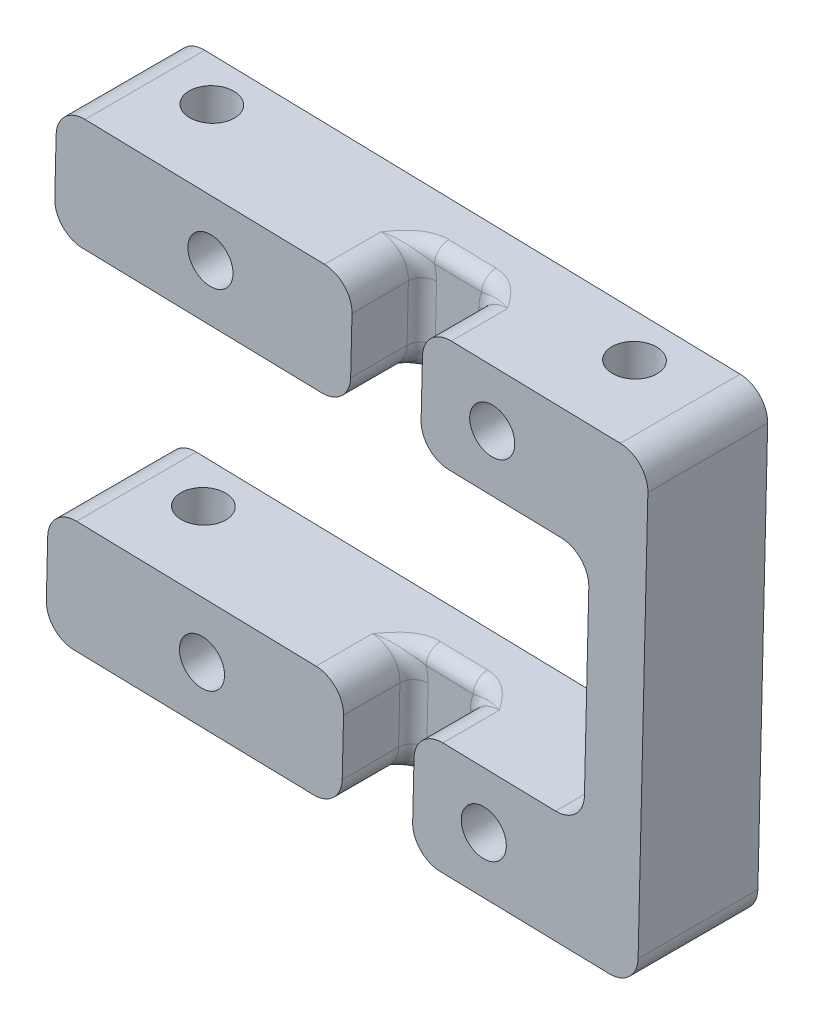
SolidWorks part; units mm, degrees
material "3003 合金"
ref_plane "前视基准面" through (0, 0, 0) normal (0, 0, 1) x (1, 0, 0)
ref_plane "上视基准面" through (0, 0, 0) normal (0, 1, 0) x (1, 0, 0)
ref_plane "右视基准面" through (0, 0, 0) normal (1, 0, 0) x (0, 0, -1)
other "Configuration Table"
sketch "草图1" plane through (0, 0, 0) normal (0, 0, 1) x (1, 0, 0)
  line L0 (19.3897, 16.0402) -> (-18.5994, 16.9503)
  line L1 (-20.6467, 14.9988) -> (-20.7425, 10.9999)
  line L2 (-18.791, 8.9526) -> (15.1993, 8.1383)
  line L3 (17.1508, 6.091) -> (16.8394, -6.9053)
  line L4 (14.7921, -8.8568) -> (-19.1981, -8.0425)
  line L5 (-21.2455, -9.994) -> (-21.3413, -13.9929)
  line L6 (-19.3897, -16.0402) -> (18.5994, -16.9503)
  line L7 (20.6467, -14.9988) -> (21.3413, 13.9929)
  arc A0 (-11.896, -12.2186) -> (-8.697, -12.2952) centre (-10.2965, -12.2569) ccw
  arc A1 (-8.697, -12.2952) -> (-11.896, -12.2186) centre (-10.2965, -12.2569) ccw
  arc A2 (-18.5994, 16.9503) -> (-20.6467, 14.9988) centre (-18.6473, 14.9509) ccw
  arc A3 (-20.7425, 10.9999) -> (-18.791, 8.9526) centre (-18.7431, 10.952) ccw
  arc A4 (17.1508, 6.091) -> (15.1993, 8.1383) centre (15.1514, 6.1389) ccw
  arc A5 (14.7921, -8.8568) -> (16.8394, -6.9053) centre (14.84, -6.8574) ccw
  arc A6 (-19.1981, -8.0425) -> (-21.2455, -9.994) centre (-19.246, -10.0419) ccw
  arc A7 (-21.3413, -13.9929) -> (-19.3897, -16.0402) centre (-19.3418, -14.0408) ccw
  arc A8 (18.5994, -16.9503) -> (20.6467, -14.9988) centre (18.6473, -14.9509) ccw
  arc A9 (21.3413, 13.9929) -> (19.3897, 16.0402) centre (19.3418, 14.0408) ccw
  arc A10 (8.697, 12.2952) -> (11.896, 12.2186) centre (10.2965, 12.2569) ccw
  arc A11 (11.896, 12.2186) -> (8.697, 12.2952) centre (10.2965, 12.2569) ccw
  arc A12 (8.0982, -12.6976) -> (11.2973, -12.7742) centre (9.6978, -12.7359) ccw
  arc A13 (11.2973, -12.7742) -> (8.0982, -12.6976) centre (9.6978, -12.7359) ccw
  arc A14 (-11.2973, 12.7742) -> (-8.0982, 12.6976) centre (-9.6978, 12.7359) ccw
  arc A15 (-8.0982, 12.6976) -> (-11.2973, 12.7742) centre (-9.6978, 12.7359) ccw
extrude "凸台-拉伸1" add sketch "草图1" along normal blind 8.5
sketch "草图2" plane through (-0.3952, -16.4953, 0) normal (-0.024, -0.9997, 0) x (0.9997, -0.024, 0)
  line L0 (-19, 8.5) -> (19, 8.5) construction
  line L1 (5, 8.5) -> (0, 8.5)
  line L2 (5, 8.5) -> (5, 3.5)
  line L3 (5, 3.5) -> (0, 3.5)
  line L4 (0, 8.5) -> (0, 3.5)
  line L5 (21, 8.5) -> (21, 0) construction
  line L6 (-19, 0) -> (19, 0) construction
  line L7 (-21, 8.5) -> (-21, 0) construction
  circle A0 centre (14.5, 3) radius 1.6
  circle A1 centre (-15.5, 3) radius 1.6
  dimension "D4" = 3.2
  dimension "D5" = 35.5
  dimension "D6" = 3
  dimension "D1" = 16
  dimension "D2" = 5
  dimension "D3" = 3.5
  dimension "D7" = 2
extrude "切除-拉伸1" cut sketch "草图2" against normal blind 47
fillet "圆角1" radius 2 8 edges at (0.3952, 16.4953, 6) (5.3937, 16.3755, 6) (5.2021, 8.3778, 6) (0.2036, 8.4976, 6) (-0.2036, -8.4976, 6) (4.795, -8.6173, 6) (4.6034, -16.615, 6) (-0.3952, -16.4953, 6)
fillet "圆角2" radius 1 16 edges at (5.3666, -9.217, 3.5) (5.203, -16.0434, 3.5) (-0.8032, -9.0692, 3.5) (-0.9668, -15.8956, 3.5) (2.8945, 16.4354, 3.5) (-0.2045, 15.9237, 3.5) (5.9653, 15.7759, 3.5) (0.2994, 12.4964, 3.5) (5.2979, 12.3767, 3.5) (-0.368, 9.0972, 3.5) (5.8018, 8.9494, 3.5) (2.7029, 8.4377, 3.5) (4.6992, -12.6162, 3.5) (-0.2994, -12.4964, 3.5) (2.2957, -8.5574, 3.5) (2.1041, -16.5551, 3.5)
